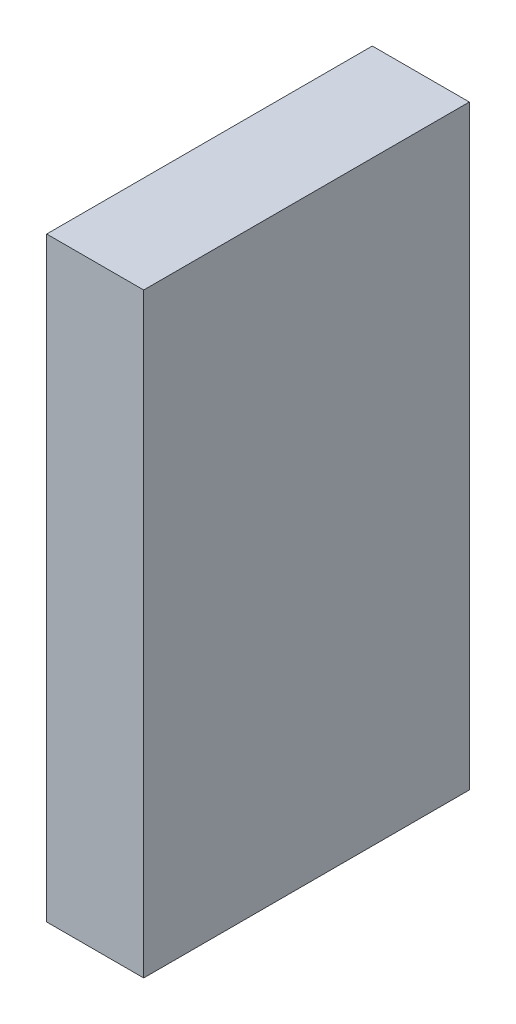
SolidWorks part; units mm, degrees
ref_plane "Front Plane" through (0, 0, 0) normal (0, 0, 1) x (1, 0, 0)
ref_plane "Top Plane" through (0, 0, 0) normal (0, 1, 0) x (1, 0, 0)
ref_plane "Right Plane" through (0, 0, 0) normal (1, 0, 0) x (0, 0, -1)
ref_axis "X-Axis" through (-88.99, 0, 0) along (1, 0, 0)
ref_axis "Y-Axis" through (0, 55, 0) along (0, -1, 0)
ref_axis "Z-Axis" through (0, 0, -88.99) along (0, 0, 1)
sketch "Sketch1" plane through (0, 0, 0) normal (0, 0, 1) x (1, 0, 0)
  line L1 (-0.35, -2.15) -> (0.35, -2.15)
  line L2 (-0.35, -2.15) -> (-0.35, 2.15)
  line L3 (-0.35, 2.15) -> (0.35, 2.15)
  line L4 (0.35, -2.15) -> (0.35, 2.15)
  line L5 (-0.35, -2.15) -> (0.35, 2.15) construction
  line L6 (-0.35, 2.15) -> (0.35, -2.15) construction
  point P0 (0, 0)
  dimension "D1" = 4.3
  dimension "D2" = 0.7
extrude "Boss-Extrude1" add sketch "Sketch1" along normal blind 2.35
